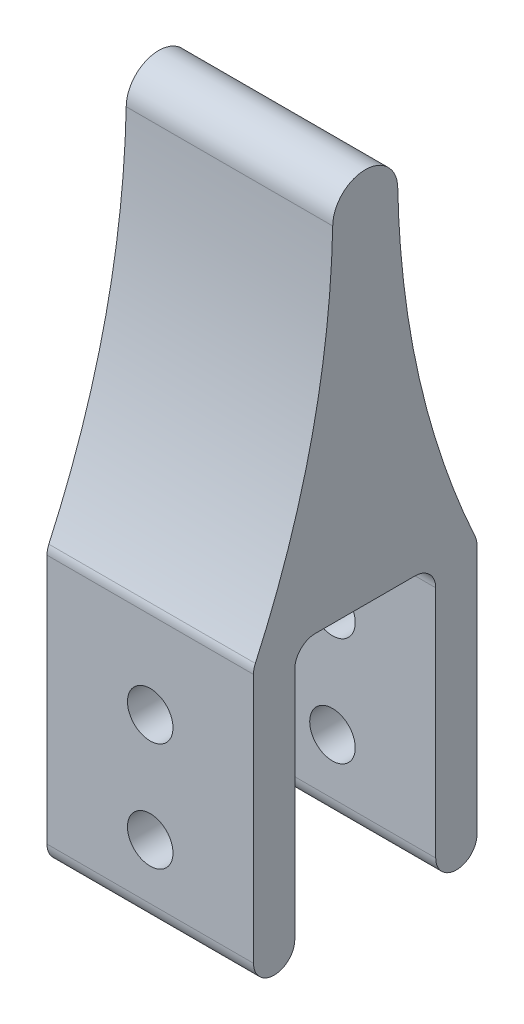
SolidWorks part; units mm, degrees
ref_plane "Front Plane" through (0, 0, 0) normal (0, 0, 1) x (1, 0, 0)
ref_plane "Top Plane" through (0, 0, 0) normal (0, 1, 0) x (1, 0, 0)
ref_plane "Right Plane" through (0, 0, 0) normal (1, 0, 0) x (0, 0, -1)
sketch "Sketch1" plane through (0, 0, 0) normal (1, 0, 0) x (0, 0, -1)
  line L0 (-6.5, 0) -> (-10.31, 0)
  line L1 (-10.31, 0) -> (-10.31, 25.4)
  line L2 (0, -1000) -> (0, 49000) construction
  line L3 (-10.31, 25.4) -> (10.31, 25.4) construction
  line L4 (-6.5, 0) -> (-6.5, 25.4)
  line L5 (-6.5, 25.4) -> (6.5, 25.4)
  line L6 (6.5, 0) -> (6.5, 25.4)
  line L7 (10.31, 0) -> (10.31, 25.4)
  line L8 (6.5, 0) -> (10.31, 0)
  arc A0 (3, 57.15) -> (-3, 57.15) centre (0, 57.15) ccw
  spline S0 degree 2 poles (-10.31, 25.4) (-3.3681, 40.4224) (-3, 57.15) knots 0 0 0 1 1 1
  spline S1 degree 2 poles (10.31, 25.4) (3.3681, 40.4224) (3, 57.15) knots 0 0 0 1 1 1
  point P10 (0, 25.4)
  point P12 (0, 25.4)
  point P14 (-6.0909, 36.6879)
  dimension "D5" = 6
  dimension "D1" = 6.5
  dimension "D2" = 3.81
  dimension "D3" = 25.4
  dimension "D4" = 31.75
  dimension "D6" = 25.4
extrude "Boss-Extrude1" add sketch "Sketch1" along normal blind 19.05
sketch "Sketch2" plane through (0, 0, -10.31) normal (0, 0, -1) x (-1, 0, 0)
  line L0 (-9.525, -974.6) -> (-9.525, 49025.4) construction
  line L1 (-19.05, 25.4) -> (0, 25.4) construction
  line L2 (-19.05, 0) -> (0, 0) construction
  circle A0 centre (-9.525, 7) radius 2.1
  circle A1 centre (-9.525, 17) radius 2.1
  point P5 (-9.525, 25.4)
  dimension "D2" = 4.2
  dimension "D3" = 4.2
  dimension "D1" = 10
  dimension "D4" = 7
extrude "Cut-Extrude1" cut sketch "Sketch2" against normal through all
fillet "Fillet2" radius 1.905 8 edges at (9.525, 25.4, -10.31) (9.525, 0, -10.31) (9.525, 0, -6.5) (9.525, 0, 6.5) (9.525, 0, 10.31) (9.525, 25.4, -6.5) (9.525, 25.4, 6.5) (9.525, 25.4, 10.31)
